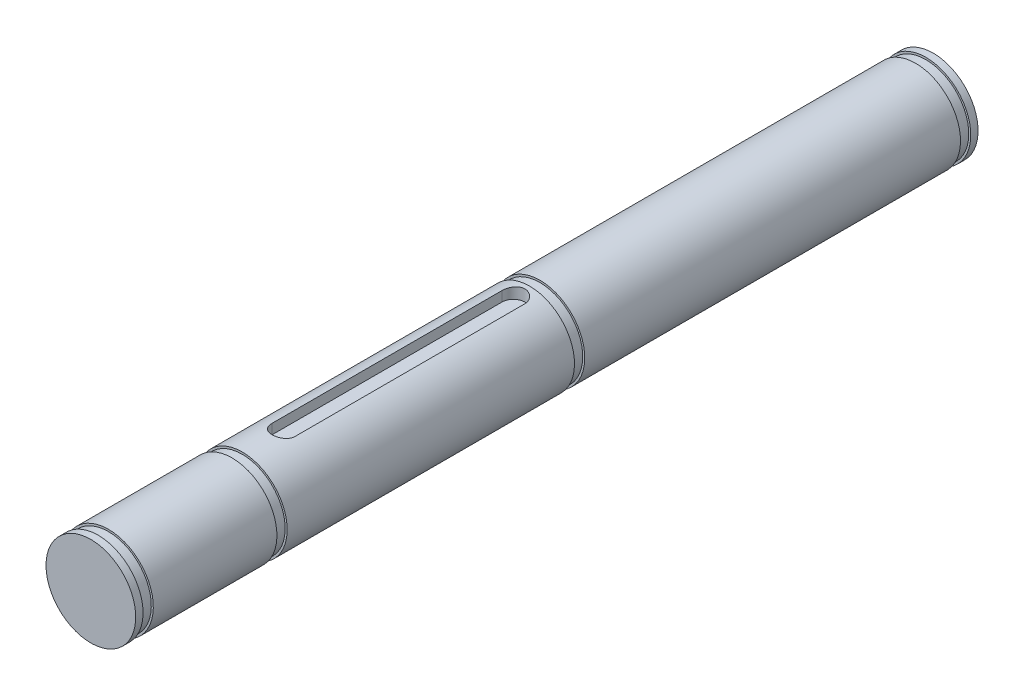
SolidWorks part; units mm, degrees
material "PET"
ref_plane "Front Plane" through (0, 0, 0) normal (0, 0, 1) x (1, 0, 0)
ref_plane "Top Plane" through (0, 0, 0) normal (0, 1, 0) x (1, 0, 0)
ref_plane "Right Plane" through (0, 0, 0) normal (1, 0, 0) x (0, 0, -1)
ref_axis "X AXIS" through (-88.99, 0, 0) along (1, 0, 0)
ref_axis "Y AXIS" through (0, 55, 0) along (0, -1, 0)
ref_axis "Z AXIS" through (0, 0, -88.99) along (0, 0, 1)
sketch "Sketch1" plane through (0, 0, 0) normal (1, 0, 0) x (0, 0, -1)
  line L0 (0, 0) -> (-23.7046, 0) construction
  line L1 (0, 0) -> (116.84, 0)
  line L2 (0, 0) -> (0, 6.223)
  line L3 (0, 6.223) -> (116.84, 6.223)
  line L4 (116.84, 0) -> (116.84, 6.223)
  line L5 (88.99, 0) -> (-88.99, 0) construction
  dimension "D1" = 12.446
  dimension "D2" = 116.84
revolve "Revolve1" add sketch "Sketch1" angle 360 about L0
sketch "Sketch3" plane through (0, 0, 0) normal (1, 0, 0) x (0, 0, -1)
  line L0 (0, 6.223) -> (0, -6.223) construction
  line L2 (0, 0) -> (0, -6.223)
  line L4 (0, 0) -> (-7.5269, 0) construction
  line L5 (116.84, -6.223) -> (116.84, 6.223) construction
  line L6 (1.016, 5.9436) -> (2.4384, 5.9436)
  line L7 (1.016, 5.9436) -> (1.016, 6.5024)
  line L8 (1.016, 6.5024) -> (2.4384, 6.5024)
  line L9 (2.4384, 5.9436) -> (2.4384, 6.5024)
  line L10 (1.016, 5.9436) -> (2.4384, 6.5024) construction
  line L11 (1.016, 6.5024) -> (2.4384, 5.9436) construction
  line L12 (60.8584, 5.9436) -> (62.2808, 5.9436)
  line L13 (60.8584, 5.9436) -> (60.8584, 6.5024)
  line L14 (60.8584, 6.5024) -> (62.2808, 6.5024)
  line L15 (62.2808, 5.9436) -> (62.2808, 6.5024)
  line L16 (60.8584, 5.9436) -> (62.2808, 6.5024) construction
  line L17 (60.8584, 6.5024) -> (62.2808, 5.9436) construction
  line L22 (116.84, 6.223) -> (0, 6.223) construction
  line L23 (19.5834, 5.9436) -> (21.0058, 5.9436)
  line L24 (114.4016, 5.9436) -> (115.824, 5.9436)
  line L25 (114.4016, 5.9436) -> (114.4016, 6.5024)
  line L26 (114.4016, 6.5024) -> (115.824, 6.5024)
  line L27 (115.824, 5.9436) -> (115.824, 6.5024)
  line L28 (114.4016, 5.9436) -> (115.824, 6.5024) construction
  line L29 (114.4016, 6.5024) -> (115.824, 5.9436) construction
  line L30 (19.5834, 5.9436) -> (19.5834, 6.5024)
  line L31 (19.5834, 6.5024) -> (21.0058, 6.5024)
  line L32 (21.0058, 5.9436) -> (21.0058, 6.5024)
  line L33 (19.5834, 5.9436) -> (21.0058, 6.5024) construction
  line L34 (19.5834, 6.5024) -> (21.0058, 5.9436) construction
  line L36 (66.7258, 5.9436) -> (68.1482, 5.9436)
  line L37 (66.7258, 5.9436) -> (66.7258, 6.5024)
  line L38 (66.7258, 6.5024) -> (68.1482, 6.5024)
  line L39 (68.1482, 5.9436) -> (68.1482, 6.5024)
  line L40 (66.7258, 5.9436) -> (68.1482, 6.5024) construction
  line L41 (66.7258, 6.5024) -> (68.1482, 5.9436) construction
  point P2 (20.2946, 6.223)
  point P6 (1.7272, 6.223)
  point P11 (61.5696, 6.223)
  point P21 (115.1128, 6.223)
  point P29 (67.437, 6.223)
  point P34 (61.5696, 6.5024)
  point P35 (67.437, 6.5024)
  dimension "D1" = 11.8872
  dimension "D2" = 1.4224
  dimension "D3" = 1.016
  dimension "D4" = 58.42
  dimension "D5" = 1.4224
  dimension "D6" = 1.4224
  dimension "D7" = 1.016
  dimension "D8" = 17.145
  dimension "D9" = 1.4224
  dimension "D10" = 4.445
  dimension "D11" = 1.4224
revolve "Cut-Revolve1" cut sketch "Sketch3" angle 360 about L4
ref_plane "Plane1" through (0, 6.223, 0) normal (0, 1, 0) x (1, 0, 0)
sketch "Sketch4" plane through (0, 6.223, 0) normal (0, 1, 0) x (1, 0, 0)
  line L0 (0, 62.2808) -> (0, 114.4016) construction
  line L8 (0, 26.7335) -> (0, 58.6105) construction
  line L9 (-1.5875, 26.7335) -> (-1.5875, 58.6105)
  line L10 (1.5875, 26.7335) -> (1.5875, 58.6105)
  arc A0 (-1.5875, 26.7335) -> (1.5875, 26.7335) centre (0, 26.7335) ccw
  arc A1 (1.5875, 58.6105) -> (-1.5875, 58.6105) centre (0, 58.6105) ccw
  point P9 (0, 42.672)
  dimension "D1" = 35.052
  dimension "D2" = 1.5875
  dimension "D3" = 42.672
extrude "Cut-Extrude1" cut sketch "Sketch4" against normal blind 1.5875
